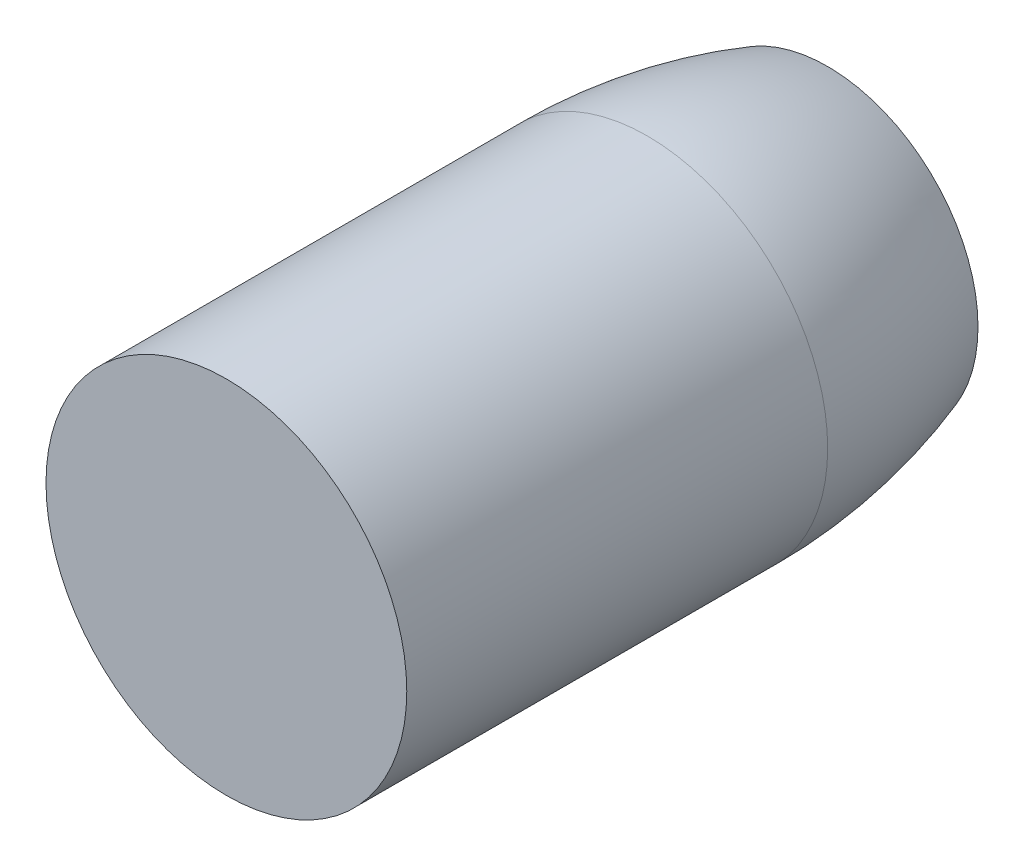
SolidWorks part; units mm, degrees
ref_plane "Top Plane" through (0, 0, 0) normal (0, 0, 1) x (1, 0, 0)
ref_plane "Front Plane" through (0, 0, 0) normal (0, 1, 0) x (1, 0, 0)
ref_plane "Right Plane" through (0, 0, 0) normal (1, 0, 0) x (0, 0, -1)
sketch "Sketch1" plane through (0, 0, 0) normal (0, 1, 0) x (1, 0, 0)
  line L0 (0, 0) -> (0, 14.2832) construction
  line L1 (0, 0) -> (6, 0)
  line L2 (6, 0) -> (6, 14)
  line L3 (5, 20) -> (4.75, 20)
  line L4 (4.75, 20) -> (4.75, 17)
  line L5 (4.75, 17) -> (0, 17)
  line L6 (0, 17) -> (0, 0)
  arc A0 (6, 14) -> (5, 20) centre (-12.5, 14) ccw
  dimension "D1" = 6
  dimension "D2" = 14
  dimension "D3" = 6
  dimension "D4" = 0.25
  dimension "D5" = 1
  dimension "D6" = 3
revolve "Revolve1" add sketch "Sketch1" angle 360 about L0
ref_axis "Axis1" through (0, 0, -14) along (0, 0, 1)
